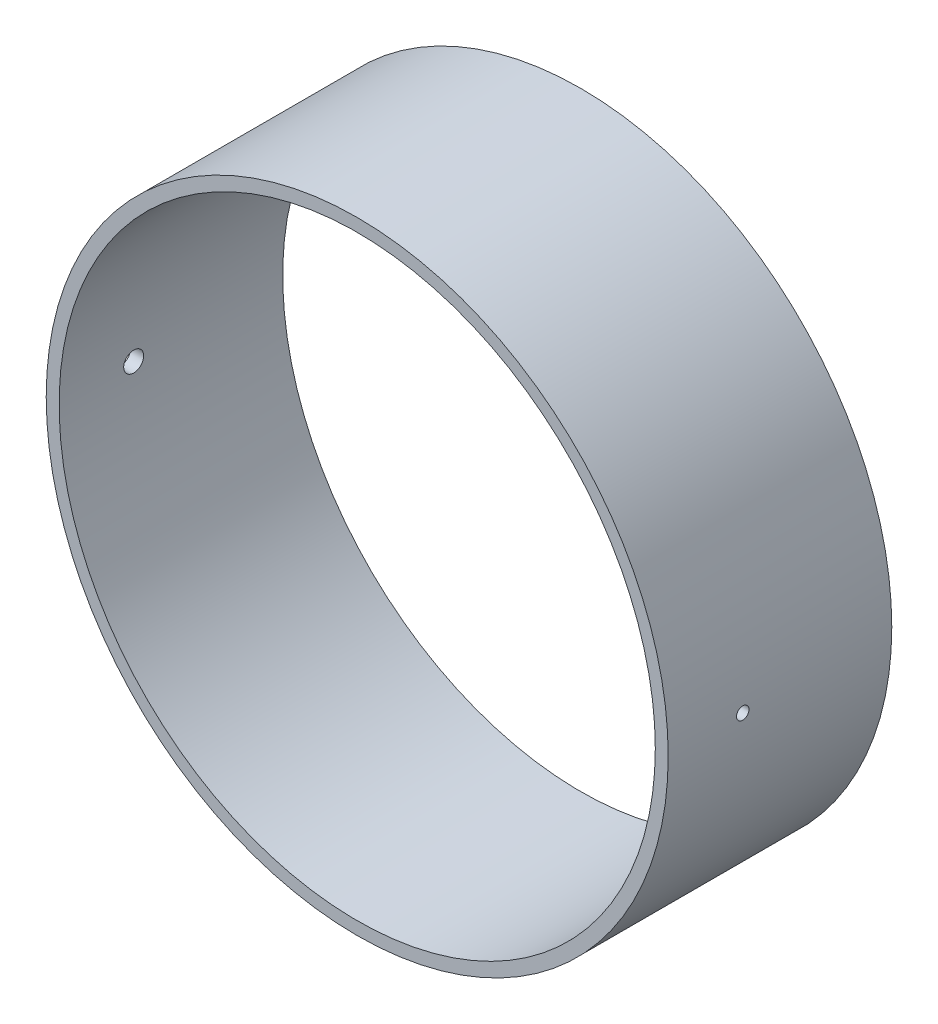
SolidWorks part; units mm, degrees
material "Silicon Dioxide"
ref_plane "Front Plane" through (0, 0, 0) normal (0, 0, 1) x (1, 0, 0)
ref_plane "Top Plane" through (0, 0, 0) normal (0, 1, 0) x (1, 0, 0)
ref_plane "Right Plane" through (0, 0, 0) normal (1, 0, 0) x (0, 0, -1)
sketch "Sketch1" plane through (0, 0, 0) normal (0, 0, 1) x (1, 0, 0)
  circle A0 centre (0, 0) radius 38.1
  circle A1 centre (0, 0) radius 39.75
  dimension "D1" = 76.2
  dimension "D2" = 79.5
extrude "Boss-Extrude1" add sketch "Sketch1" along normal blind 28.575
ref_plane "Plane1" through (-39.75, 0, 0) normal (-1, 0, 0) x (0, 0, 1)
sketch "Sketch2" plane through (-39.75, 0, 0) normal (-1, 0, 0) x (0, 0, 1)
  line L0 (0, 39.75) -> (0, -39.75) construction
  circle A0 centre (19.05, 0) radius 1.27
  point P4 (0, 0)
  dimension "D1" = 2.54
  dimension "D2" = 19.05
extrude "Cut-Extrude1" cut sketch "Sketch2" against normal blind 10 contours A0
sketch "Sketch3" plane through (-39.75, 0, 0) normal (-1, 0, 0) x (0, 0, 1)
  circle A0 centre (19.05, 0) radius 0.7937
  dimension "D1" = 1.5875
extrude "Cut-Extrude2" cut sketch "Sketch3" against normal through all
